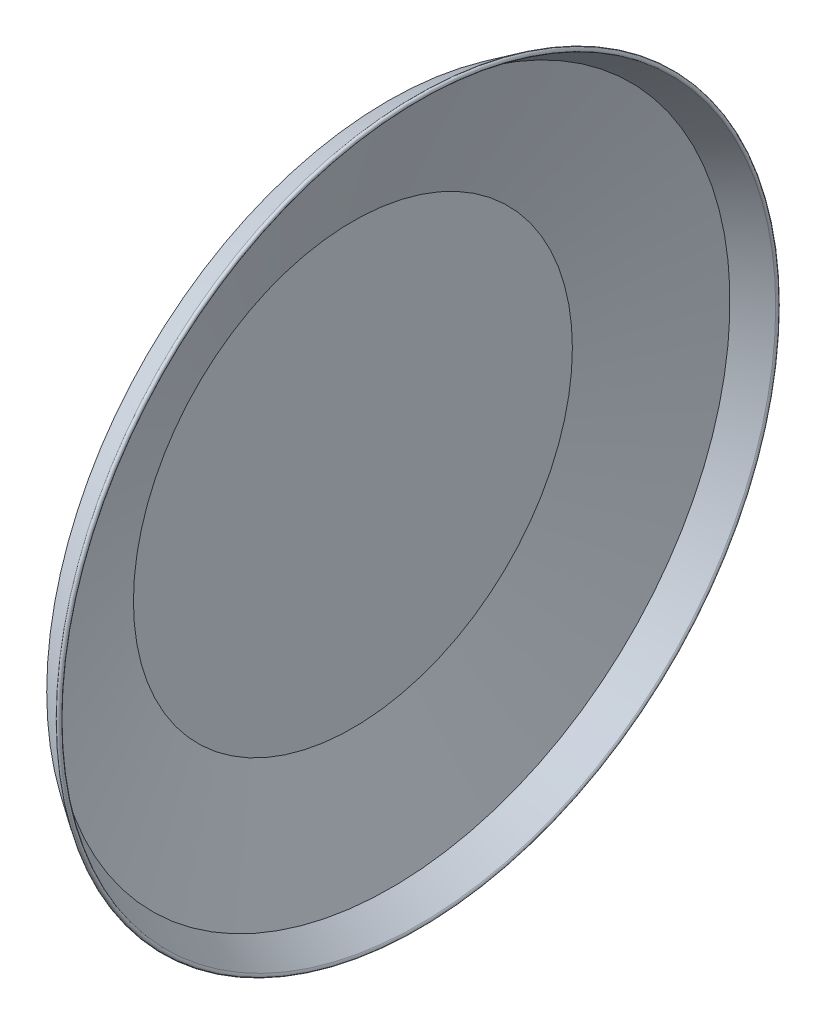
SolidWorks part; units mm, degrees
ref_plane "Front Plane" through (0, 0, 0) normal (0, 0, 1) x (1, 0, 0)
ref_plane "Top Plane" through (0, 0, 0) normal (0, 1, 0) x (1, 0, 0)
ref_plane "Right Plane" through (0, 0, 0) normal (1, 0, 0) x (0, 0, -1)
sketch "Sketch1" plane through (0, 0, 0) normal (0, 0, 1) x (1, 0, 0)
  line L0 (0, 0) -> (-148.0369, 0) construction
  line L8 (-67.0148, 0) -> (-67.0148, 51.9187)
  line L9 (-67.0148, 51.9187) -> (-57.7632, 80.4647)
  line L13 (-57.7632, 80.4647) -> (-51.025, 85)
  line L14 (-66.0148, 0) -> (-66.0148, 51.7607)
  line L15 (-66.0148, 51.7607) -> (-56.9183, 79.8279)
  line L16 (-56.9183, 79.8279) -> (-50.4666, 84.1704)
  line L17 (-67.0148, 0) -> (-66.0148, 0)
  arc A3 (-51.025, 85) -> (-50.4666, 84.1704) centre (-50.7458, 84.5852) cw
  point P5 (-67.0188, 44.656)
  point P12 (-62.5097, 62.5756)
  point P13 (-66.0148, 51.7607)
  point P14 (-37.8885, 85)
  dimension "D1" = 170
  dimension "D2" = 1
revolve "Revolve2" add sketch "Sketch1" angle 360 about L17
